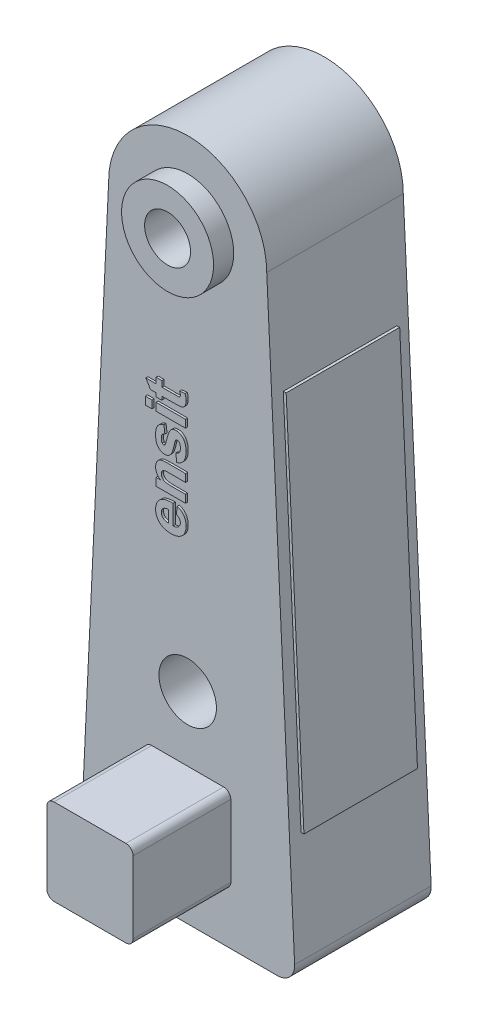
SolidWorks part; units mm, degrees
material "Alliage 6061"
ref_plane "Plan de face" through (0, 0, 0) normal (0, 0, 1) x (1, 0, 0)
ref_plane "Plan de dessus" through (0, 0, 0) normal (0, 1, 0) x (1, 0, 0)
ref_plane "Plan de droite" through (0, 0, 0) normal (1, 0, 0) x (0, 0, -1)
sketch "Esquisse1" plane through (0, 0, 0) normal (0, 0, 1) x (1, 0, 0)
  line L0 (0, -140) -> (0, 280) construction
  line L1 (-62.415, -140) -> (62.415, -140)
  line L2 (74.4014, -127.4292) -> (55, 280)
  line L3 (-55, 280) -> (-74.4014, -127.4292)
  arc A0 (55, 280) -> (-55, 280) centre (0, 280) ccw
  arc A1 (-62.415, -140) -> (-74.4014, -127.4292) centre (-62.415, -128) cw
  arc A2 (62.415, -140) -> (74.4014, -127.4292) centre (62.415, -128) ccw
  point P9 (-75, -140)
  point P12 (75, -140)
  dimension "D4" = 55
  dimension "D6" = 12
  dimension "D7" = 12
  dimension "D1" = 150
  dimension "D2" = 140
  dimension "D3" = 280
  dimension "D5" = 110
extrude "Boss.-Extru.1" add sketch "Esquisse1" along normal blind 95
sketch "Esquisse2" plane through (0, 0, 95) normal (0, 0, 1) x (1, 0, 0)
  line L0 (0, 0) -> (0, 280) construction
  circle A0 centre (0, 0) radius 20
  circle A1 centre (0, 280) radius 16
  dimension "D2" = 40
  dimension "D3" = 32
  dimension "D1" = 280
extrude "Enlèv. mat.-Extru.1" cut sketch "Esquisse2" against normal through all
sketch "Esquisse3" plane through (0, 0, 95) normal (0, 0, 1) x (1, 0, 0)
  line L0 (0, 0) -> (0, 280) construction
  circle A0 centre (0, 280) radius 32
  circle A1 centre (0, 280) radius 16
  dimension "D2" = 64
  dimension "D3" = 32
  dimension "D1" = 280
extrude "Boss.-Extru.2" add sketch "Esquisse3" along normal blind 14
sketch "Esquisse4" plane through (0, 0, 95) normal (0, 0, 1) x (1, 0, 0)
  line L0 (0, 0) -> (0, -75) construction
  line L2 (-25, -105) -> (25, -105)
  line L3 (-30, -100) -> (-30, -50)
  line L4 (-25, -45) -> (25, -45)
  line L5 (30, -100) -> (30, -50)
  line L6 (-30, -105) -> (30, -45) construction
  line L7 (-30, -45) -> (30, -105) construction
  arc A0 (-25, -105) -> (-30, -100) centre (-25, -100) cw
  arc A1 (25, -105) -> (30, -100) centre (25, -100) ccw
  arc A2 (-30, -50) -> (-25, -45) centre (-25, -50) cw
  arc A3 (25, -45) -> (30, -50) centre (25, -50) cw
  dimension "D4" = 5
  dimension "D5" = 5
  dimension "D6" = 5
  dimension "D7" = 5
  dimension "D1" = 75
  dimension "D2" = 60
  dimension "D3" = 60
extrude "Boss.-Extru.3" add sketch "Esquisse4" along normal blind 68
sketch "Esquisse5" plane through (68.1787, 3.2466, 0) normal (0.9989, 0.0476, 0) x (0, 0, -1)
  line L0 (-47.5, -130.8239) -> (-47.5, 277.067) construction
  line L1 (-87, -56.8733) -> (-8, -56.8733)
  line L2 (-87, -56.8733) -> (-87, 203.1164)
  line L3 (-87, 203.1164) -> (-8, 203.1164)
  line L4 (-8, -56.8733) -> (-8, 203.1164)
  line L5 (-87, -56.8733) -> (-8, 203.1164) construction
  line L6 (-87, 203.1164) -> (-8, -56.8733) construction
  line L7 (-95, -130.8239) -> (0, -130.8239) construction
  line L8 (-95, 277.067) -> (0, 277.067) construction
  line L9 (-95, 73.1215) -> (0, 73.1215) construction
  line L10 (-95, -130.8239) -> (-95, 277.067) construction
  line L11 (0, -130.8239) -> (0, 277.067) construction
  dimension "D1" = 8
  dimension "D2" = 79
  dimension "D3" = 259.9896
extrude "Boss.-Extru.4" add sketch "Esquisse5" along normal blind 2
sketch "Esquisse6" plane through (0, 0, 95) normal (0, 0, 1) x (1, 0, 0)
  line L0 (0, 65) -> (0, 205) construction
  text T0 "ensit" font "Arial" height 28
  dimension "D1" = 65
  dimension "D2" = 140
extrude "Boss.-Extru.5" add sketch "Esquisse6" along normal blind 1.5
ref_axis "Axis_J2" through (0, 0, 0) along (0, 0, 1)
ref_axis "Axis_J3" through (0, 280, 0) along (0, 0, 1)
